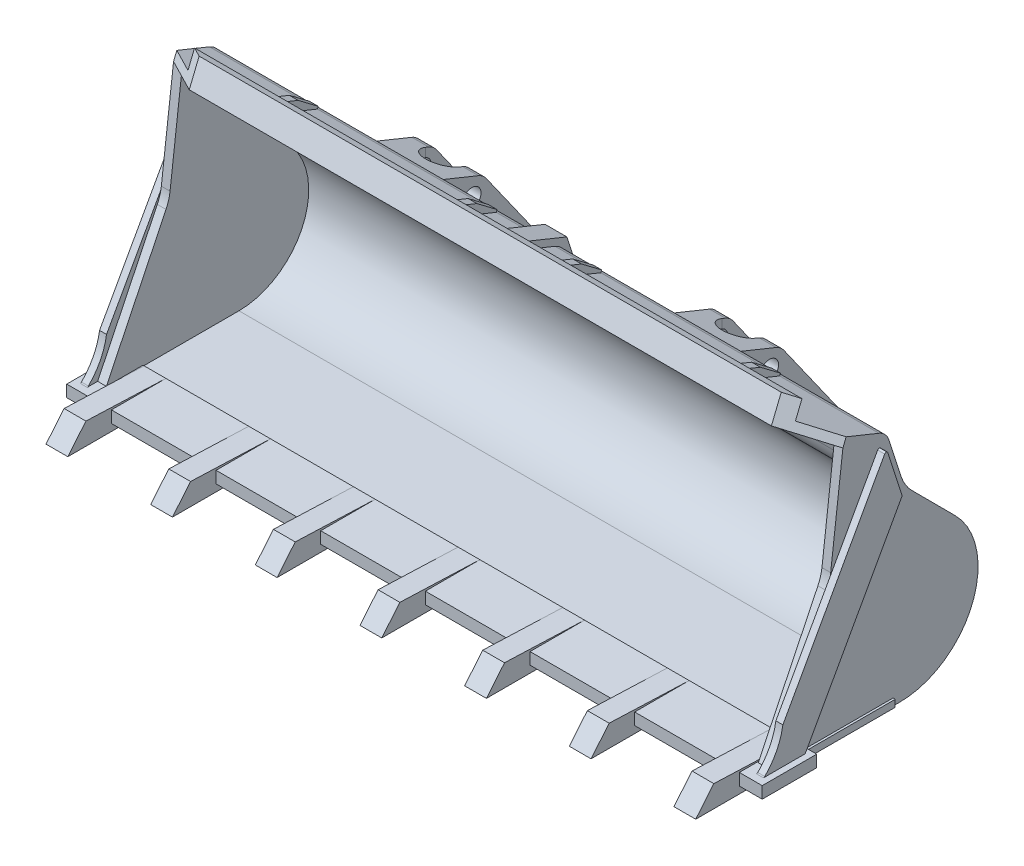
SolidWorks part; units mm, degrees
ref_plane "Front Plane" through (0, 0, 0) normal (0, 0, 1) x (1, 0, 0)
ref_plane "Top Plane" through (0, 0, 0) normal (0, 1, 0) x (1, 0, 0)
ref_plane "Right Plane" through (0, 0, 0) normal (1, 0, 0) x (0, 0, -1)
sketch "Sketch1" plane through (0, 0, 0) normal (1, 0, 0) x (0, 0, -1)
  line L0 (15.25, 0) -> (0, 0)
  line L1 (0, 0) -> (0, 1)
  line L2 (0, 1) -> (7.25, 16)
  line L3 (7.25, 16) -> (8.75, 28.5)
  line L4 (8.75, 28.5) -> (5.5533, 29.7974)
  line L5 (5.5533, 29.7974) -> (6.6814, 32.5772)
  line L6 (6.6814, 32.5772) -> (7.608, 32.2011)
  line L7 (7.608, 32.2011) -> (6.8559, 30.348)
  line L8 (6.8559, 30.348) -> (13.7401, 27.5539)
  line L9 (13.7401, 27.5539) -> (15.7923, 21.2039)
  line L10 (15.7923, 21.2039) -> (21.624, 15.3539)
  arc A0 (21.624, 15.3539) -> (15.25, 0) centre (15.25, 9) cw
  point P15 (17.0315, 24.4632)
  point P16 (12.7764, 27.3299)
  point P17 (8.4316, 31.4955)
  point P18 (5.1296, 35.3663)
  point P19 (7.9676, 30.9804)
  point P20 (10.7438, 29.1479)
  point P21 (7.3286, 31.3074)
  point P22 (20.3806, 22.8839)
  point P23 (22.853, 20.173)
  point P24 (19.9116, 24.1773)
  dimension "D7" = 3.45
  dimension "D15" = 9
  dimension "D1" = 1
  dimension "D2" = 15
  dimension "D3" = 7.25
  dimension "D4" = 28.5
  dimension "D5" = 8.75
  dimension "D6" = 15.25
  dimension "D8" = 2
  dimension "D9" = 1
  dimension "D10" = 1
  dimension "D11" = 130
  dimension "D12" = 153
  dimension "D13" = 6.35
  dimension "D14" = 5.85
extrude "Boss-Extrude1" add sketch "Sketch1" along normal blind 38.375
fillet "Fillet1" radius 5 1 edges at (19.1875, 21.2039, -15.7923)
fillet "Fillet2" radius 2 1 edges at (19.1875, 27.5539, -13.7401)
fillet "Fillet3" radius 5 1 edges at (19.1875, 16, -7.25)
shell "Shell1" thickness 1 removed face at (0, 19.8023, -10.049) removed face at (19.1875, 0.5, 0) removed face at (19.1875, 8.1243, -3.4434) removed face at (19.1875, 16.029, -7.1509) removed face at (19.1875, 22.6643, -8.0497)
sketch "Sketch2" plane through (0, 0, 0) normal (1, 0, 0) x (0, 0, -1)
  line L0 (0, 1) -> (0, 0) construction
  line L1 (-2, 1.1) -> (4.25, 1.1)
  line L2 (-2, 1.1) -> (-2, -0.25)
  line L3 (-2, -0.25) -> (4.25, -0.25)
  line L4 (4.25, 1.1) -> (4.25, -0.25)
  line L6 (0, 0) -> (15.25, 0) construction
  point P6 (-2, 1.7524)
  point P9 (-2, 1.0667)
  dimension "D1" = 6.25
  dimension "D2" = 1.35
  dimension "D3" = 2
  dimension "D4" = 0.25
extrude "Boss-Extrude2" add sketch "Sketch2" along normal blind 39.875
sketch "Sketch3" plane through (0, 0, 0) normal (1, 0, 0) x (0, 0, -1)
  line L1 (4.25, 0) -> (14.5, 0)
  line L2 (4.25, 0) -> (4.25, 0.8)
  line L3 (4.25, 0.8) -> (14.5, 0.8)
  line L4 (14.5, 0) -> (14.5, 0.8)
  dimension "D1" = 10.25
  dimension "D2" = 0.8
extrude "Boss-Extrude3" add sketch "Sketch3" along normal blind 38.625
sketch "Sketch4" plane through (38.375, 0, 0) normal (1, 0, 0) x (0, 0, -1)
  line L0 (-1.4, 0.8) -> (3.4593, 0.8)
  line L1 (3.4593, 0.8) -> (14.7517, 21.1721)
  line L2 (14.7517, 21.1721) -> (12.962, 26.7098)
  line L3 (12.962, 26.7098) -> (1.0667, 5.25)
  line L4 (15.4232, 22.3462) -> (14.0269, 26.6665) construction
  line L5 (-2, 1.1) -> (-2, -0.25) construction
  line L6 (4.25, 1.1) -> (-2, 1.1) construction
  line L7 (1.0667, 5.25) -> (-1.4, 0.8) construction
  arc A0 (1.0667, 5.25) -> (-1.4, 0.8) centre (-6.1511, 6.3423) cw
  dimension "D5" = 7.3
  dimension "D1" = 1
  dimension "D2" = 61
  dimension "D3" = 0.6
  dimension "D4" = 0.3
  dimension "D6" = 4.45
  dimension "D7" = 4.25
extrude "Boss-Extrude4" add sketch "Sketch4" along normal blind 0.8
fillet "Fillet4" radius 0.2 3 edges at (38.775, 1.1, 1.0709) (38.775, 21.1721, -14.7517) (38.775, 26.7098, -12.962)
sketch "Sketch5" plane through (0, 28.445, -11.5446) normal (0, 0.9266, -0.3761) x (1, 0, 0)
  line L0 (38.375, -2.6101) -> (38.375, -6.0601)
  line L1 (38.375, -6.0601) -> (33.375, -6.0601)
  line L2 (38.375, -6.0601) -> (0, -6.0601) construction
  line L3 (33.375, -6.0601) -> (38.375, -2.6101)
  dimension "D1" = 5
extrude "Cut-Extrude1" cut sketch "Sketch5" against normal up to next and the other way through all
sketch "Sketch6" plane through (0, 0, 0) normal (1, 0, 0) x (0, 0, -1)
  line L1 (12.876, 27.9047) -> (6.8559, 30.348) construction
  line L2 (15.4232, 22.3462) -> (14.0269, 26.6665) construction
  line L3 (12.876, 27.9047) -> (9.1696, 29.4089)
  line L4 (9.1696, 29.4089) -> (9.4516, 30.1039)
  line L5 (9.4516, 30.1039) -> (14.2253, 28.1665)
  line L6 (14.2253, 28.1665) -> (15.568, 24.0118)
  line L7 (14.9495, 23.8119) -> (15.568, 24.0118)
  line L8 (14.9495, 23.8119) -> (14.0269, 26.6665)
  arc A0 (14.0269, 26.6665) -> (12.876, 27.9047) centre (12.1238, 26.0515) ccw construction
  arc A1 (14.0269, 26.6665) -> (12.876, 27.9047) centre (12.1238, 26.0515) ccw
  dimension "D1" = 0.75
  dimension "D3" = 4
  dimension "D4" = 3
extrude "Boss-Extrude5" add sketch "Sketch6" along normal blind 1.25
sketch "Sketch7" plane through (0, 28.445, -11.5446) normal (0, 0.9266, -0.3761) x (1, 0, 0)
  line L0 (38.375, 1.4368) -> (1.25, 1.4368) construction
  line L1 (5.5, 1.4368) -> (6.5, 1.4368)
  line L2 (5.5, 1.4368) -> (5.5, -5.0601)
  line L3 (5.5, -5.0601) -> (6.5, -5.0601)
  line L4 (6.5, 1.4368) -> (6.5, -5.0601)
  line L5 (34.8243, -5.0601) -> (0, -5.0601) construction
  line L6 (34.8243, -5.0601) -> (0, -5.0601) construction
  line L7 (26, 1.4368) -> (27, 1.4368)
  line L8 (26, 1.4368) -> (26, -5.0601)
  line L9 (26, -5.0601) -> (27, -5.0601)
  line L10 (27, 1.4368) -> (27, -5.0601)
  line L11 (0, -2.5632) -> (0, -5.0601) construction
  dimension "D1" = 5.5
  dimension "D2" = 1
  dimension "D3" = 1
  dimension "D4" = 20.5
extrude "Boss-Extrude6" add sketch "Sketch7" along normal blind 1
chamfer "Chamfer1" distance 0.75 angle 75 2 edges at (26.5, 28.8313, -13.252) (6, 28.8313, -13.252) first distance on face at (26.5, 28.368, -13.064) first distance on face at (6, 28.368, -13.064)
mirror "Mirror1" about plane through (0, 0, 0) normal (1, 0, 0) of bodies 107
sketch "Sketch8" plane through (0, 0, 0) normal (1, 0, 0) x (0, 0, -1)
  line L0 (4.25, 0) -> (14.5, 0) construction
  line L1 (14.5, 0) -> (15.25, 0) construction
  line L2 (21.624, 15.3539) -> (16.6398, 20.3538) construction
  line L3 (15.4232, 22.3462) -> (14.0269, 26.6665) construction
  line L4 (4.25, 0) -> (14.5, 0)
  line L5 (14.5, 0) -> (15.25, 0)
  line L6 (21.624, 15.3539) -> (16.6398, 20.3538)
  line L7 (15.4232, 22.3462) -> (14.0269, 26.6665)
  line L8 (4.25, 0) -> (4.25, -0.125)
  line L9 (4.25, -0.25) -> (4.25, 1.1) construction
  line L10 (4.25, -0.125) -> (27.531, -0.125)
  line L11 (29.0172, 1.5781) -> (27.6549, 11.545)
  line L12 (26.7847, 13.7529) -> (19.4614, 24.1194)
  line L13 (14.0269, 26.6665) -> (18.58, 24.8186)
  line L14 (6.8559, 30.348) -> (12.876, 27.9047) construction
  arc A0 (15.25, 0) -> (21.624, 15.3539) centre (15.25, 9) ccw construction
  arc A1 (15.4232, 22.3462) -> (16.6398, 20.3538) centre (20.1809, 23.8838) ccw construction
  arc A2 (15.25, 0) -> (21.624, 15.3539) centre (15.25, 9) ccw
  arc A3 (15.4232, 22.3462) -> (16.6398, 20.3538) centre (20.1809, 23.8838) ccw
  arc A4 (27.6549, 11.545) -> (26.7847, 13.7529) centre (22.701, 10.8679) ccw
  arc A5 (18.58, 24.8186) -> (19.4614, 24.1194) centre (17.8279, 22.9654) cw
  arc A6 (27.531, -0.125) -> (29.0172, 1.5781) centre (27.531, 1.375) ccw
  point P8 (27.4496, 25.1234)
  point P18 (26.3667, 12.5512)
  point P21 (27.4895, 12.7552)
  point P24 (19.1232, 24.5982)
  point P27 (29.25, -0.125)
  dimension "D6" = 5
  dimension "D7" = 2
  dimension "D8" = 1.5
  dimension "D1" = 5.5
  dimension "D2" = 25
  dimension "D3" = 0.125
  dimension "D4" = 13
  dimension "D5" = 14.5
extrude "Boss-Extrude7" add sketch "Sketch8" along normal mid plane 41.75 separate body
sketch "Sketch9" plane through (0, 0, 0) normal (0, 1, 0) x (1, 0, 0)
  line L0 (0, -9.1212) -> (0, 36.4453) construction
  line L1 (-18.95, 18.2316) -> (-18.95, 39.241)
  line L2 (-13.25, 1.8263) -> (13.25, 1.8263)
  line L3 (-13.25, 1.8263) -> (-13.25, 39.241)
  line L4 (-13.25, 39.241) -> (13.25, 39.241)
  line L5 (13.25, 1.8263) -> (13.25, 39.241)
  line L6 (-37.375, 15.9316) -> (37.375, 15.9316) construction
  line L7 (15.05, 18.2316) -> (15.05, 39.241)
  line L8 (15.05, 39.241) -> (18.95, 39.241)
  line L9 (18.95, 18.2316) -> (18.95, 39.241)
  line L10 (-15.05, 39.241) -> (-18.95, 39.241)
  line L11 (-15.05, 18.2316) -> (-15.05, 39.241)
  line L12 (20.875, 27.531) -> (-20.875, 27.531) construction
  arc A0 (15.05, 18.2316) -> (18.95, 18.2316) centre (17, 18.2316) ccw
  arc A1 (-18.95, 18.2316) -> (-15.05, 18.2316) centre (-17, 18.2316) ccw
  point P16 (16.9, 19.3314)
  dimension "D4" = 0.35
  dimension "D1" = 37.9
  dimension "D2" = 30.1
  dimension "D3" = 26.5
  dimension "D5" = 11.71
extrude "Cut-Extrude2" cut sketch "Sketch9" against normal blind 41.75 and the other way through all
sketch "Sketch10" plane through (0, 0, 0) normal (1, 0, 0) x (0, 0, -1)
  circle A0 centre (27.531, 1.375) radius 1.05
  circle A1 centre (17.8279, 22.9654) radius 1.05
  dimension "D1" = 2.1
  dimension "D2" = 2.1
extrude "Cut-Extrude3" cut sketch "Sketch10" against normal through all both and the other way through all
combine bodies "Combine1" operation type add bodies to combine 108 113 112
sketch "Sketch12" plane through (0, 0, 0) normal (1, 0, 0) x (0, 0, -1)
  line L0 (4.25, 1.1) -> (3.75, -0.25)
  line L1 (-2, -0.25) -> (4.25, -0.25) construction
  line L2 (3.75, -0.25) -> (3.75, -1.05)
  line L3 (3.75, -1.05) -> (-7, -1.05)
  line L4 (-7, -1.05) -> (-4.9233, 1.45)
  line L5 (-4.9233, 1.45) -> (4.25, 1.1)
  line L6 (4.25, -0.25) -> (4.25, 1.1) construction
  line L7 (-2, 1.1) -> (-2, -0.25) construction
  dimension "D1" = 0.8
  dimension "D2" = 0.5
  dimension "D3" = 5
  dimension "D4" = 3.25
  dimension "D5" = 2.5
extrude "Boss-Extrude8" add sketch "Sketch12" along normal mid plane 2.5
pattern_linear "LPattern1" count 4 spacing 12 along (-1, 0, 0) count 4 spacing 12 along (1, 0, 0) of "Boss-Extrude8"
